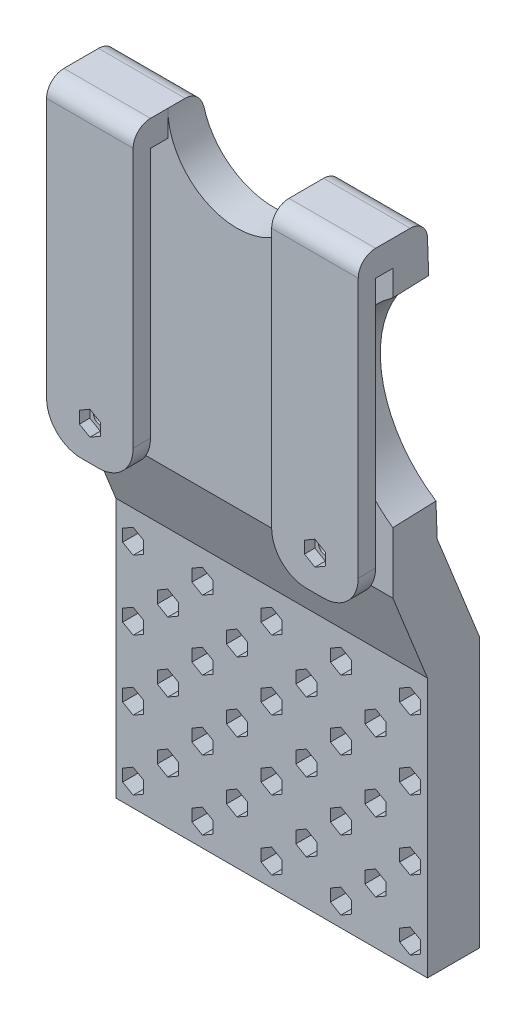
SolidWorks part; units mm, degrees
ref_plane "前视基准面" through (0, 0, 0) normal (0, 0, 1) x (1, 0, 0)
ref_plane "上视基准面" through (0, 0, 0) normal (0, 1, 0) x (1, 0, 0)
ref_plane "右视基准面" through (0, 0, 0) normal (1, 0, 0) x (0, 0, -1)
other "Configuration Table"
sketch "草图1" plane through (0, 0, 0) normal (1, 0, 0) x (0, 0, -1)
  line L0 (-2.5, 0) -> (-2.5, 82.5)
  line L1 (-2.5, 82.5) -> (2.5, 82.5)
  line L5 (7.5033, 90) -> (-2.5, 90)
  line L6 (-7.5, 85) -> (-7.5, 0)
  line L7 (-7.5, 0) -> (-2.5, 0)
  line L8 (-2.5, 0) -> (2.5, 0) construction
  line L9 (2.5, 82.5) -> (12.5, 82.5) construction
  line L10 (12.5, 82.5) -> (12.5, 85.1824) construction
  line L11 (0, 82.5) -> (0, 0) construction
  line L12 (2.5, 82.5) -> (2.5, 0)
  line L13 (2.5, 0) -> (12.5, -25)
  line L14 (12.5, -25) -> (12.5, -100)
  line L15 (12.5, -100) -> (27.5, -100)
  line L16 (27.5, -100) -> (27.5, -22.1113)
  line L17 (27.5, -22.1113) -> (15.3038, 8.3792)
  line L18 (12.5, 85.1824) -> (15.3038, 8.3792)
  line L19 (2.5, 0) -> (2.5, -25) construction
  line L20 (2.5, -25) -> (12.5, -25) construction
  arc A0 (-2.5, 90) -> (-7.5, 85) centre (-2.5, 85) ccw
  arc A1 (12.5, 85.1824) -> (7.5033, 90) centre (7.5033, 85) ccw
  point P8 (0, 0)
  point P20 (15.3038, 8.3792)
  dimension "D6" = 5
  dimension "D1" = 5
  dimension "D2" = 10
  dimension "D3" = 5
  dimension "D4" = 82.5
  dimension "D5" = 7.5
  dimension "D7" = 100
  dimension "D8" = 15
  dimension "D9" = 15
  dimension "D10" = 10
  dimension "D11" = 25
extrude "凸台-拉伸1" add sketch "草图1" along normal blind 45 and the other way blind 45
sketch "草图2" plane through (0, 0, 7.5) normal (0, 0, 1) x (1, 0, 0)
  line L0 (-20, 0) -> (20, 0)
  line L1 (-45, 0) -> (45, 0) construction
  line L2 (20, 0) -> (20, 90)
  line L3 (-45, 90) -> (45, 90) construction
  line L4 (20, 90) -> (-20, 90)
  line L5 (-20, 90) -> (-20, 0)
  line L6 (-45, 85) -> (-45, 0) construction
  point P8 (0, 0)
  dimension "D1" = 25
extrude "切除-拉伸1" cut sketch "草图2" against normal up to surface (10 mm away) up to face at (0, 41.25, -2.5)
sketch "草图3" plane through (0, 0, -2.5) normal (0, 0, 1) x (1, 0, 0)
  line L0 (-20, 90) -> (20, 90) construction
  line L1 (20, 90) -> (-20, 90)
  arc A0 (-20, 90) -> (20, 90) centre (0, 90) ccw
extrude "切除-拉伸2" cut sketch "草图3" against normal through all
sketch "草图4" plane through (0, 0.5691, -15.5889) normal (0, 0.0365, -0.9993) x (-1, 0, 0)
  line L4 (-1045, 46.2425) -> (48955, 46.2425) construction
  line L5 (-45, 7.8153) -> (-45, 84.6697) construction
  line L7 (0, -1000) -> (0, 49000) construction
  line L8 (-45, 74.9653) -> (-45, 17.5197)
  line L9 (45, 74.9653) -> (45, 17.5197)
  arc A2 (-45, 74.9653) -> (-45, 17.5197) centre (-65, 46.2425) cw
  arc A3 (45, 74.9653) -> (45, 17.5197) centre (65, 46.2425) ccw
  point P5 (-45, 46.2425)
  dimension "D1" = 20
  dimension "D2" = 35
extrude "切除-拉伸3" cut sketch "草图4" against normal up to surface (10.3609 mm away) up to face at (0, 61.25, -2.5)
fillet "圆角1" radius 10 4 edges at (20, 0, 5) (45, 0, 5) (-20, 0, 5) (-45, 0, 5)
sketch "草图6" plane through (0, 0, 7.5) normal (0, 0, 1) x (1, 0, 0)
  line L0 (-32.5, -1000) -> (-32.5, 49000) construction
  line L1 (-35, 0) -> (-30, 0) construction
  line L2 (0, -1000) -> (0, 49000) construction
  line L3 (-45, 0) -> (45, 0) construction
  line L4 (-45, 10) -> (-32.5, 10) construction
  circle A0 centre (-32.5, 10) radius 2
  circle A1 centre (-32.5, 10) radius 3.5 construction
  circle A2 centre (32.5, 10) radius 2
  point P5 (-32.5, 0)
  point P10 (0, 0)
  dimension "D1" = 4
  dimension "D2" = 7
extrude "切除-拉伸4" cut sketch "草图6" against normal through all
sketch "草图7" plane through (0, 0, 7.5) normal (0, 0, 1) x (1, 0, 0)
  line L0 (0, -1000) -> (0, 49000) construction
  line L1 (-32.5, 13.5) -> (-35.5311, 11.75)
  line L2 (-35.5311, 11.75) -> (-35.5311, 8.25)
  line L3 (-35.5311, 8.25) -> (-32.5, 6.5)
  line L4 (-32.5, 6.5) -> (-29.4689, 8.25)
  line L5 (-29.4689, 8.25) -> (-29.4689, 11.75)
  line L6 (-29.4689, 11.75) -> (-32.5, 13.5)
  line L7 (29.4689, 11.75) -> (32.5, 13.5)
  line L8 (29.4689, 8.25) -> (29.4689, 11.75)
  line L9 (32.5, 6.5) -> (29.4689, 8.25)
  line L10 (35.5311, 8.25) -> (32.5, 6.5)
  line L11 (35.5311, 11.75) -> (35.5311, 8.25)
  line L12 (32.5, 13.5) -> (35.5311, 11.75)
  circle A0 centre (-32.5, 10) radius 3.5 construction
  circle A1 centre (32.5, 10) radius 3.5 construction
  point P12 (-35.7868, 11.8035)
  point P13 (-32.4289, 13.8014)
  point P14 (-35.7431, 8.6837)
  dimension "D2" = 7
  dimension "D1" = 120
  dimension "D3" = 120
extrude "切除-拉伸5" cut sketch "草图7" against normal blind 3
sketch "草图8" plane through (0, 0, -27.5) normal (0, 0, -1) x (-1, 0, 0)
  line L0 (0, -1000) -> (0, 49000) construction
  line L1 (32.5, 13.5) -> (29.4689, 11.75)
  line L2 (29.4689, 11.75) -> (29.4689, 8.25)
  line L3 (29.4689, 8.25) -> (32.5, 6.5)
  line L4 (32.5, 6.5) -> (35.5311, 8.25)
  line L5 (35.5311, 8.25) -> (35.5311, 11.75)
  line L6 (35.5311, 11.75) -> (32.5, 13.5)
  line L7 (-35.5311, 11.75) -> (-32.5, 13.5)
  line L8 (-35.5311, 8.25) -> (-35.5311, 11.75)
  line L9 (-32.5, 6.5) -> (-35.5311, 8.25)
  line L10 (-29.4689, 8.25) -> (-32.5, 6.5)
  line L11 (-29.4689, 11.75) -> (-29.4689, 8.25)
  line L12 (-32.5, 13.5) -> (-29.4689, 11.75)
  circle A0 centre (32.5, 10) radius 3.5 construction
  circle A1 centre (-32.5, 10) radius 3.5 construction
  dimension "D1" = 7
  dimension "D2" = 120
  dimension "D3" = 120
extrude "切除-拉伸6" cut sketch "草图8" against normal offset from surface (22 mm away) 3 up to face at (-32.5, 8, -2.5)
sketch "草图9" plane through (0, 0, -27.5) normal (0, 0, -1) x (-1, 0, 0)
  line L0 (0, -1000) -> (0, 49000) construction
  line L1 (-20, -1022.1113) -> (-20, 48977.8887) construction
  line L3 (20, -1022.1113) -> (20, 48977.8887) construction
  line L5 (-30, -1015.9428) -> (-30, 48984.0572) construction
  line L7 (-10, -1014.8908) -> (-10, 48985.1092) construction
  line L8 (-40, -1022.1113) -> (-40, 48977.8887) construction
  line L10 (-20, -33.2679) -> (0, -33.2679) construction
  line L11 (0, -33.2679) -> (20, -33.2679) construction
  line L12 (40, -1022.1113) -> (40, 48977.8887) construction
  line L14 (10, -1014.8908) -> (10, 48985.1092) construction
  line L15 (30, -1014.1017) -> (30, 48985.8983) construction
  line L16 (-20, -33.2679) -> (-40, -33.2679) construction
  line L17 (20, -33.2679) -> (40, -33.2679) construction
  line L18 (-30, -43.735) -> (-10, -43.735) construction
  line L19 (-10, -43.735) -> (10, -43.735) construction
  line L20 (10, -43.735) -> (30, -43.735) construction
  circle A0 centre (-20, -33.2679) radius 2
  circle A1 centre (0, -33.2679) radius 2
  circle A2 centre (20, -33.2679) radius 2
  circle A3 centre (-10, -43.735) radius 2
  circle A4 centre (10, -43.735) radius 2
  circle A5 centre (-40, -33.2679) radius 2
  circle A6 centre (40, -33.2679) radius 2
  circle A7 centre (-30, -43.735) radius 2
  circle A8 centre (30, -43.735) radius 2
  dimension "D1" = 4
  dimension "D2" = 4
  dimension "D3" = 4
  dimension "D7" = 4
  dimension "D8" = 4
  dimension "D14" = 4
  dimension "D15" = 4
  dimension "D16" = 4
  dimension "D17" = 4
  dimension "D4" = 20
  dimension "D5" = 20
  dimension "D6" = 20
  dimension "D9" = 20
  dimension "D10" = 10
  dimension "D11" = 10
  dimension "D12" = 10
  dimension "D13" = 10
extrude "切除-拉伸7" cut sketch "草图9" against normal through all
pattern_linear "阵列(线性)1" count 24 spacing 20 along (0, -1, 0) of "切除-拉伸7"
sketch "草图10" plane through (0, 0, -12.5) normal (0, 0, 1) x (1, 0, 0)
  line L0 (-40, -29.7679) -> (-43.0311, -31.5179)
  line L1 (-43.0311, -31.5179) -> (-43.0311, -35.0179)
  line L2 (-43.0311, -35.0179) -> (-40, -36.7679)
  line L3 (-40, -36.7679) -> (-36.9689, -35.0179)
  line L4 (-36.9689, -35.0179) -> (-36.9689, -31.5179)
  line L5 (-36.9689, -31.5179) -> (-40, -29.7679)
  line L6 (-16.9689, -31.5179) -> (-20, -29.7679)
  line L7 (-16.9689, -35.0179) -> (-16.9689, -31.5179)
  line L8 (-20, -36.7679) -> (-16.9689, -35.0179)
  line L9 (-23.0311, -35.0179) -> (-20, -36.7679)
  line L10 (-23.0311, -31.5179) -> (-23.0311, -35.0179)
  line L11 (-20, -29.7679) -> (-23.0311, -31.5179)
  line L12 (3.0311, -31.5179) -> (0, -29.7679)
  line L13 (3.0311, -35.0179) -> (3.0311, -31.5179)
  line L14 (0, -36.7679) -> (3.0311, -35.0179)
  line L15 (-3.0311, -35.0179) -> (0, -36.7679)
  line L16 (-3.0311, -31.5179) -> (-3.0311, -35.0179)
  line L17 (0, -29.7679) -> (-3.0311, -31.5179)
  line L18 (23.0311, -31.5179) -> (20, -29.7679)
  line L19 (23.0311, -35.0179) -> (23.0311, -31.5179)
  line L20 (20, -36.7679) -> (23.0311, -35.0179)
  line L21 (16.9689, -35.0179) -> (20, -36.7679)
  line L22 (16.9689, -31.5179) -> (16.9689, -35.0179)
  line L23 (20, -29.7679) -> (16.9689, -31.5179)
  line L24 (43.0311, -31.5179) -> (40, -29.7679)
  line L25 (43.0311, -35.0179) -> (43.0311, -31.5179)
  line L26 (40, -36.7679) -> (43.0311, -35.0179)
  line L27 (36.9689, -35.0179) -> (40, -36.7679)
  line L28 (36.9689, -31.5179) -> (36.9689, -35.0179)
  line L29 (40, -29.7679) -> (36.9689, -31.5179)
  line L30 (-30, -40.235) -> (-33.0311, -41.985)
  line L31 (-33.0311, -41.985) -> (-33.0311, -45.485)
  line L32 (-33.0311, -45.485) -> (-30, -47.235)
  line L33 (-30, -47.235) -> (-26.9689, -45.485)
  line L34 (-26.9689, -45.485) -> (-26.9689, -41.985)
  line L35 (-26.9689, -41.985) -> (-30, -40.235)
  line L36 (-6.9689, -41.985) -> (-10, -40.235)
  line L37 (-10, -40.235) -> (-13.0311, -41.985)
  line L38 (-13.0311, -41.985) -> (-13.0311, -45.485)
  line L39 (-6.9689, -45.485) -> (-6.9689, -41.985)
  line L40 (-10, -47.235) -> (-6.9689, -45.485)
  line L41 (-13.0311, -45.485) -> (-10, -47.235)
  line L42 (13.0311, -41.985) -> (10, -40.235)
  line L43 (10, -40.235) -> (6.9689, -41.985)
  line L44 (6.9689, -41.985) -> (6.9689, -45.485)
  line L45 (13.0311, -45.485) -> (13.0311, -41.985)
  line L46 (10, -47.235) -> (13.0311, -45.485)
  line L47 (6.9689, -45.485) -> (10, -47.235)
  line L48 (33.0311, -41.985) -> (30, -40.235)
  line L49 (30, -40.235) -> (26.9689, -41.985)
  line L50 (26.9689, -41.985) -> (26.9689, -45.485)
  line L51 (33.0311, -45.485) -> (33.0311, -41.985)
  line L52 (30, -47.235) -> (33.0311, -45.485)
  line L53 (26.9689, -45.485) -> (30, -47.235)
  circle A0 centre (-40, -33.2679) radius 3.5 construction
  circle A1 centre (-30, -43.735) radius 3.5 construction
  dimension "D2" = 7
  dimension "D4" = 7
  dimension "D1" = 120
  dimension "D5" = 120
  dimension "D3" = 5
  dimension "D6" = 4
extrude "切除-拉伸8" cut sketch "草图10" against normal offset from surface (12 mm away) 3 up to face at (-40, -91.2679, -27.5)
pattern_linear "阵列(线性)2" count 5 spacing 20 along (0, -1, 0) of "切除-拉伸8"
